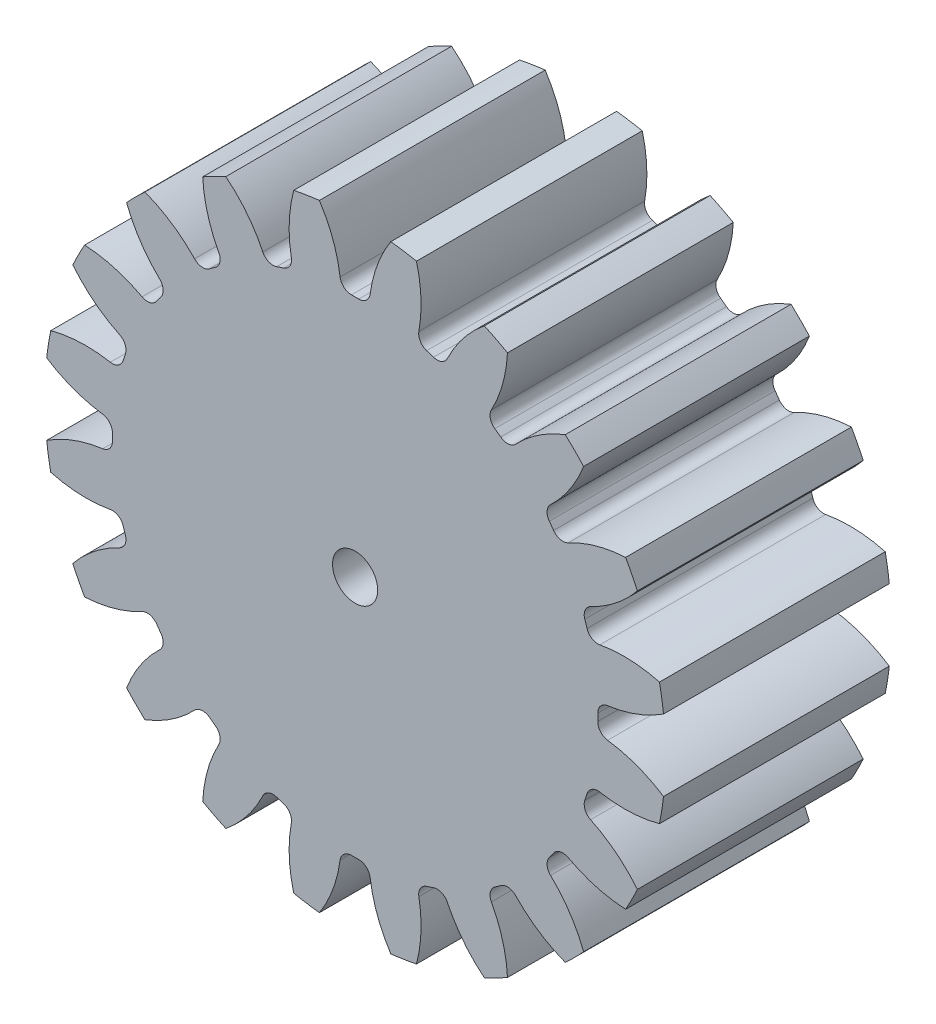
SolidWorks part; units mm, degrees
ref_plane "Front Plane" through (0, 0, 0) normal (0, 0, 1) x (1, 0, 0)
ref_plane "Top Plane" through (0, 0, 0) normal (0, 1, 0) x (1, 0, 0)
ref_plane "Right Plane" through (0, 0, 0) normal (1, 0, 0) x (0, 0, -1)
sketch "Sketch1" plane through (0, 0, 0) normal (0, 0, 1) x (1, 0, 0)
  circle A0 centre (0, 0) radius 31.75
  circle A1 centre (0, 0) radius 34.925
  circle A2 centre (0, 0) radius 27.305
  circle A3 centre (0, 0) radius 2.54
  dimension "D1" = 63.5
  dimension "D2" = 69.85
  dimension "D4" = 5.08
  dimension "D3" = 7.62
extrude "Boss-Extrude2" add sketch "Sketch1" along normal mid plane 25.4 contours A1
sketch "Sketch2" plane through (0, 0, 12.7) normal (0, 0, 1) x (1, 0, 0)
  line L0 (0, 0) -> (0, 37.465) construction
  line L1 (-2.4911, 31.6521) -> (2.4911, 31.6521) construction
  line L2 (-1.5759, 27.2595) -> (0, 0) construction
  line L3 (0, 0) -> (5.8608, 37.0037) construction
  line L4 (0, 24.8083) -> (-4.5076, 37.1928) construction
  line L5 (2.4911, 31.6521) -> (7.4119, 30.8727) construction
  arc A0 (-5.8608, 37.0037) -> (-1.5759, 27.2595) centre (-16.7993, 26.3794) cw
  arc A1 (5.8608, 37.0037) -> (1.5759, 27.2595) centre (16.7993, 26.3794) ccw
  circle A2 centre (0, 0) radius 27.305 construction
  arc A3 (-1.5759, 27.2595) -> (1.5759, 27.2595) centre (0, 0) cw
  circle A4 centre (0, 0) radius 31.75 construction
  circle A6 centre (0, 0) radius 37.465
  arc A7 (5.8608, 37.0037) -> (-5.8608, 37.0037) centre (0, 0) ccw
  point P13 (0, 0)
  point P17 (0, 0)
  circle M2 centre (0, 0) radius 34.925
  dimension "D2" = 20
  dimension "D3" = 9
  dimension "D1" = 2.54
extrude "Cut-Extrude3" cut sketch "Sketch2" against normal through all and the other way through all contours A0 A3 A1 M2 region at (0, 31.7047, 12.7)
fillet "Fillet1" radius 1.27 1 edges at (-1.5759, 27.2595, 0)
fillet "Fillet2" radius 1.27 1 edges at (1.5759, 27.2595, 0)
pattern_circular "CirPattern2" count 20 over 360 about axis through (0, 0, 12.7) along (0, 0, -1) of "Fillet2", "Cut-Extrude3", "Fillet1" reverse direction yes
extrude "Cut-Extrude4" cut sketch "Sketch1<4>" against normal through all both and the other way through all contours A3
sketch "Sketch1<4>" plane through (0, 0, 0) normal (0, 0, 1) x (1, 0, 0) same geometry as "Sketch1"
equation "\"Module\" = .125in"
equation "\"N\"= 20"
equation "\"D1@Sketch1\"= \"Module\" * \"N\""
equation "\"D2@Sketch1\"=(\"N\" + 2) * \"Module\""
equation "\"D3@Sketch1\"=\"Module\" * if(\"Module\"=> 1.25, 2.25,2.4)"
equation "\"D3@Sketch2\"=180 / \"N\""
equation "\"D1@CirPattern2\"=\"N\""
